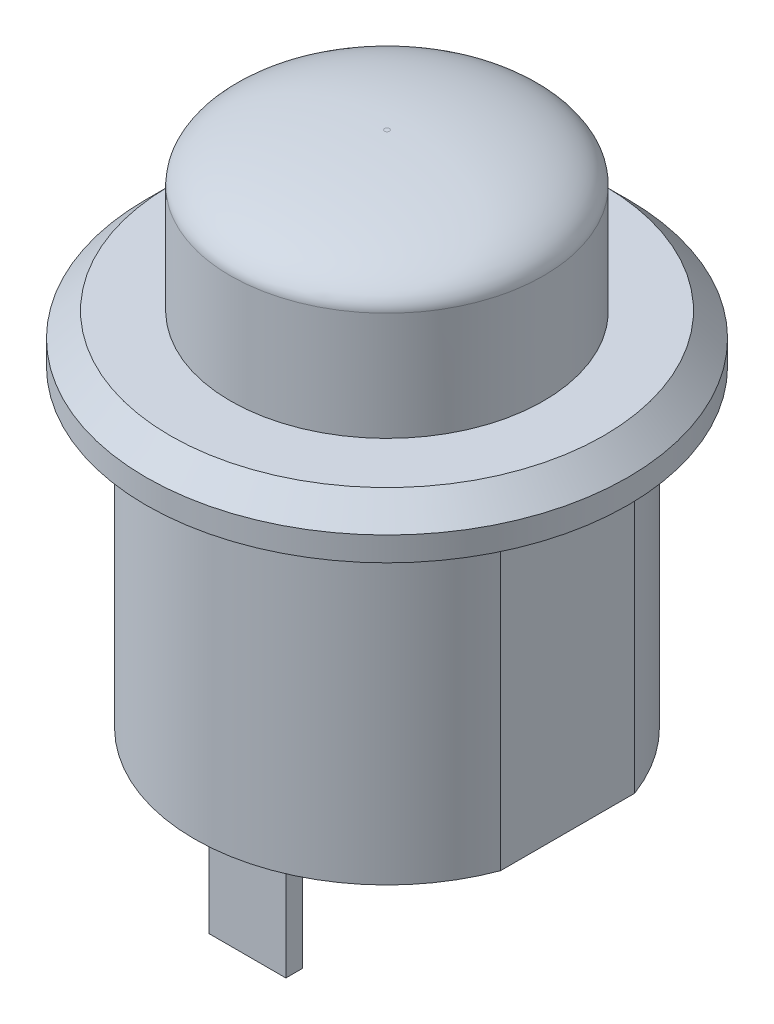
SolidWorks part; units mm, degrees
ref_plane "Front Plane" through (0, 0, 0) normal (0, 0, 1) x (1, 0, 0)
ref_plane "Top Plane" through (0, 0, 0) normal (0, 1, 0) x (1, 0, 0)
ref_plane "Right Plane" through (0, 0, 0) normal (1, 0, 0) x (0, 0, -1)
sketch "Sketch1" plane through (0, 0, 0) normal (0, 1, 0) x (1, 0, 0)
  line L0 (-7.5, 2.7839) -> (-7.5, -2.7839)
  line L1 (7.5, -2.7839) -> (7.5, 2.7839)
  arc A0 (7.5, 2.7839) -> (-7.5, 2.7839) centre (0, 0) ccw
  arc A1 (-7.5, -2.7839) -> (7.5, -2.7839) centre (0, 0) ccw
  point P4 (7.5, 0)
  point P6 (0, 0)
  point P7 (0, 0)
  point P9 (0, 0)
  point P10 (0, 0)
  point P11 (0, 0)
  point P12 (0, 0)
  point P13 (0, 0)
  dimension "D2" = 8
  dimension "D3" = 8
  dimension "D1" = 15
extrude "Boss-Extrude1" add sketch "Sketch1" along normal blind 13
sketch "Sketch2" plane through (0, 13, 0) normal (0, 1, 0) x (1, 0, 0)
  circle A0 centre (0, 0) radius 10
  dimension "D1" = 20
extrude "Boss-Extrude2" add sketch "Sketch2" along normal blind 2
chamfer "Chamfer1" distance 1 angle 45 1 edges at (0, 15, 10)
sketch "Sketch3" plane through (0, 15, 0) normal (0, 1, 0) x (1, 0, 0)
  circle A0 centre (0, 0) radius 6.5
  dimension "D1" = 13
extrude "Boss-Extrude3" add sketch "Sketch3" along normal blind 6.5
fillet "Fillet1" radius 2 1 edges at (0, 21.5, 6.5) second distance 6.4 first distance on face at (0, 21.5, 6.5)
sketch "Sketch4" plane through (0, 0, 0) normal (0, -1, 0) x (1, 0, 0)
  line L0 (11, 0) -> (-11, 0) construction
  line L1 (-1.6, 5.8) -> (1.6, 5.8)
  line L2 (-1.6, 5.8) -> (-1.6, 5.1)
  line L3 (-1.6, 5.1) -> (1.6, 5.1)
  line L4 (1.6, 5.8) -> (1.6, 5.1)
  line L5 (-1.6, -5.1) -> (1.6, -5.1)
  line L6 (-1.6, -5.1) -> (-1.6, -5.8)
  line L7 (-1.6, -5.8) -> (1.6, -5.8)
  line L8 (1.6, -5.1) -> (1.6, -5.8)
  line L9 (0, -11) -> (0, 11) construction
  point P10 (0, -5.1)
  dimension "D1" = 0.7
  dimension "D2" = 0.7
  dimension "D3" = 3.2
  dimension "D4" = 3.2
  dimension "D5" = 10.2
  dimension "D6" = 5.1
extrude "Boss-Extrude4" add sketch "Sketch4" along normal blind 5.3
